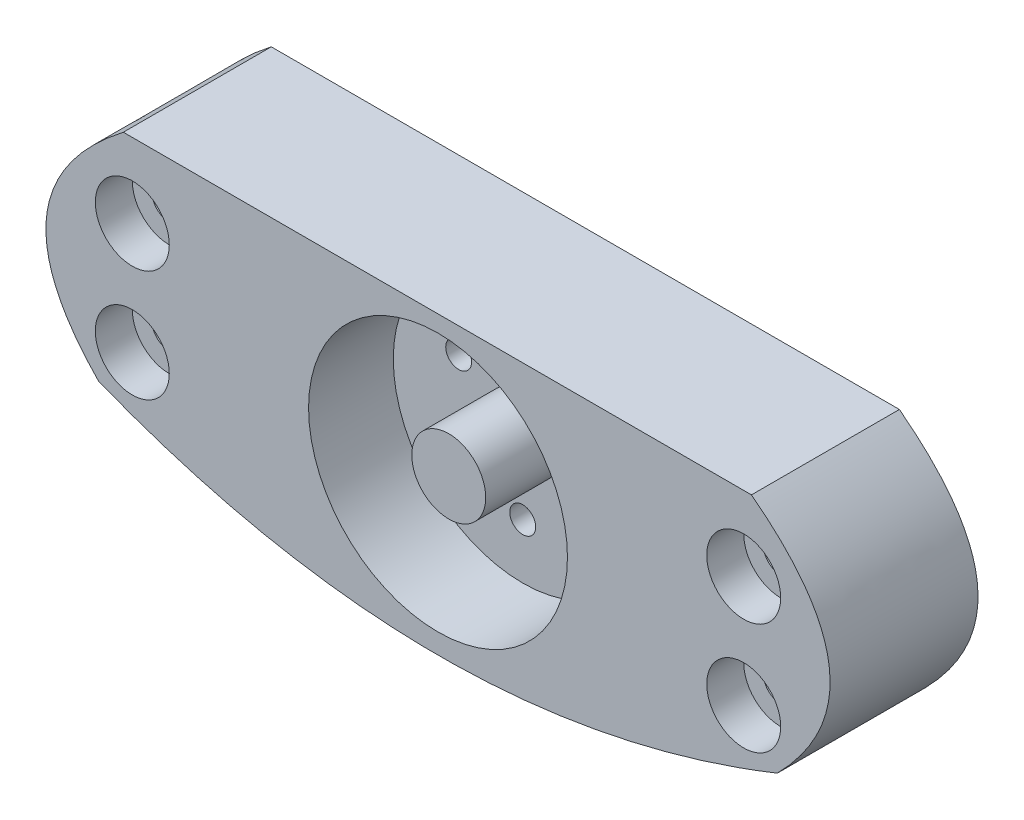
SolidWorks part; units mm, degrees
ref_plane "Front Plane" through (0, 0, 0) normal (0, 0, 1) x (1, 0, 0)
ref_plane "Top Plane" through (0, 0, 0) normal (0, 1, 0) x (1, 0, 0)
ref_plane "Right Plane" through (0, 0, 0) normal (1, 0, 0) x (0, 0, -1)
sketch "Sketch2" plane through (0, 0, 0) normal (0, 0, 1) x (1, 0, 0)
  line L1 (42.3768, 8.6832) -> (-42.5401, 8.6832)
  line L2 (42.3768, 8.6832) -> (-42.5401, 8.6832)
  parabola Q3 (45.8737, -22.1555) -> (42.3768, 8.6832) focus (46.195, -7.6248) apex (52.9944, -7.3425)
  parabola Q4 (-42.5401, 8.6832) -> (-45.8737, -22.1555) focus (-46.1445, -7.62) apex (-52.997, -7.3593)
  parabola Q5 (-45.8737, -22.1555) -> (45.8737, -22.1555) focus (0.744, 26.3908) apex (1.3864, -31.2701)
  parabola Q6 (45.8737, -22.1555) -> (42.3768, 8.6832) focus (46.195, -7.6248) apex (52.9944, -7.3425)
  parabola Q7 (-42.5401, 8.6832) -> (-45.8737, -22.1555) focus (-46.1445, -7.62) apex (-52.997, -7.3593)
  parabola Q8 (-45.8737, -22.1555) -> (45.8737, -22.1555) focus (0.744, 26.3908) apex (1.3864, -31.2701)
  dimension "D1" = 0
extrude "Boss-Extrude1" add sketch "Sketch2" along normal blind 20
sketch "Sketch4" plane through (0, 0, 20) normal (0, 0, 1) x (1, 0, 0)
  line L1 (0, -17) -> (0, -2) construction
  circle A1 centre (0, -11.063) radius 17.5
  dimension "D1" = 35
extrude "Cut-Extrude1" cut sketch "Sketch4" against normal blind 11.4533
sketch "Sketch5" plane through (0, 0, 8.5467) normal (0, 0, 1) x (1, 0, 0)
  line L0 (0, -17) -> (0, -2) construction
  circle A1 centre (0, -11.063) radius 5
  circle A2 centre (0, -11.063) radius 17.5 construction
  dimension "D1" = 10
extrude "Boss-Extrude2" add sketch "Sketch5" along normal blind 10
sketch "Sketch6" plane through (0, 0, 8.5467) normal (0, 0, 1) x (1, 0, 0)
  line L0 (0, -17) -> (0, -2) construction
  line L1 (0, -21.1295) -> (8.6603, -6.1295)
  line L2 (8.6603, -6.1295) -> (-8.6603, -6.1295)
  line L3 (-8.6603, -6.1295) -> (0, -21.1295)
  circle A0 centre (0, -11.1295) radius 10
  dimension "D1" = 20
hole_wizard "CBORE for M5 Hex Head Machine Screw2" positions "Sketch9" profile "Sketch10" counterbore size "M5" standard "ANSI Metric"
sketch "Sketch9" plane through (0, 0, 0) normal (0, 0, -1) x (-1, 0, 0)
  point P0 (-8.6603, -6.1295)
  point P3 (0, -21.1295)
  point P6 (8.6603, -6.1295)
sketch "Sketch10" plane through (8.6603, -6.1295, 0) normal (1, 0, 0) x (0, 1, 0)
  line L0 (0, 0) -> (0, 12.75)
  line L1 (0, 12.75) -> (1.75, 11)
  line L2 (1.75, 11) -> (1.75, 4)
  line L3 (1.75, 4) -> (3.5, 4)
  line L4 (3.5, 4) -> (3.5, 0)
  line L5 (3.5, 0) -> (0, 0)
  line L10 (0, 12.75) -> (-1.75, 11) construction
  line L11 (0, -6.35) -> (0, 107.95) construction
  dimension "Hole Dia." = 3.5
  dimension "Hole Depth" = 11
  dimension "C'Bore Dia." = 7
  dimension "C'Bore Depth" = 4
  dimension "Drill Angle" = 90
sketch "Sketch11" plane through (0, 0, 20) normal (0, 0, 1) x (1, 0, 0)
  point P0 (41.3295, -16.4796)
  point P1 (41.3295, -1.4009)
  point P2 (0, 0)
  point P3 (-41.3295, -16.4796)
  point P4 (-41.3295, -1.4009)
  point P5 (0, 0)
sketch "Sketch18" plane through (0, 0, 0) normal (0, 0, 1) x (1, 0, 0)
  circle A0 centre (0, -11.063) radius 35.18 construction
  circle A1 centre (0, -11.063) radius 17.5
  circle A2 centre (0, -11.063) radius 17.5 construction
  dimension "D2" = 70.36
  dimension "D1" = 0
hole_wizard "CBORE for M5 Hex Head Bolt2" positions "Sketch19" profile "Sketch20" counterbore size "M5" standard "ANSI Metric"
sketch "Sketch19" plane through (0, 0, 20) normal (0, 0, 1) x (1, 0, 0)
  point P0 (41.3295, -1.4009)
  point P3 (41.3295, -16.4796)
  point P7 (-41.3295, -1.4009)
  point P10 (-41.3295, -16.4796)
  point P14 (0, 0)
  point P15 (43.7774, -18.3159)
  point P17 (41.711, -6.1808)
  point P19 (-43.2127, -5.3624)
  point P21 (-43.8576, -16.4796)
sketch "Sketch20" plane through (41.3295, -1.4009, 20) normal (1, 0, 0) x (0, -1, 0)
  line L0 (0, 0) -> (0, 12.35)
  line L1 (0, 12.35) -> (2.35, 10)
  line L2 (2.35, 10) -> (2.35, 5)
  line L3 (2.35, 5) -> (5, 5)
  line L4 (5, 5) -> (5, 0)
  line L5 (5, 0) -> (0, 0)
  line L10 (0, 12.35) -> (-2.35, 10) construction
  line L11 (0, -6.35) -> (0, 107.95) construction
  dimension "Hole Dia." = 4.7
  dimension "Hole Depth" = 10
  dimension "C'Bore Dia." = 10
  dimension "C'Bore Depth" = 5
  dimension "Drill Angle" = 90
